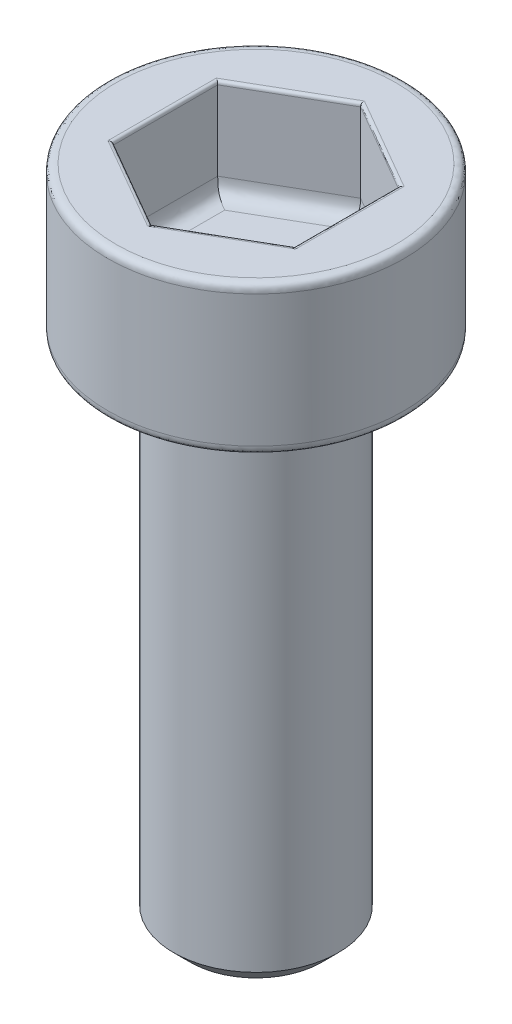
SolidWorks part; units mm, degrees
ref_plane "Front Plane" through (0, 0, 0) normal (0, 0, 1) x (1, 0, 0)
ref_plane "Top Plane" through (0, 0, 0) normal (0, 1, 0) x (1, 0, 0)
ref_plane "Right Plane" through (0, 0, 0) normal (1, 0, 0) x (0, 0, -1)
sketch "Sketch2" plane through (0, 0, 0) normal (1, 0, 0) x (0, 0, -1)
  line L0 (0, 0) -> (0, 40)
  line L1 (0, 40) -> (9, 40)
  line L2 (9, 40) -> (9, 31)
  line L3 (9, 31) -> (5, 31)
  line L4 (5, 31) -> (5, 0)
  line L5 (5, 0) -> (0, 0)
  dimension "D1" = 5
  dimension "D2" = 9
  dimension "D3" = 9
  dimension "D4" = 40
revolve "Revolve1" add sketch "Sketch2" angle 360 about L0
chamfer "Chamfer1" distance 1 angle 45 1 edges at (0, 0, -5)
sketch "Sketch3" plane through (0, 40, 0) normal (0, 1, 0) x (1, 0, 0)
  line L1 (0, 6.3509) -> (-5.5, 3.1754)
  line L2 (-5.5, 3.1754) -> (-5.5, -3.1754)
  line L3 (-5.5, -3.1754) -> (0, -6.3509)
  line L4 (0, -6.3509) -> (5.5, -3.1754)
  line L5 (5.5, -3.1754) -> (5.5, 3.1754)
  line L6 (5.5, 3.1754) -> (0, 6.3509)
  circle A0 centre (0, 0) radius 5.5 construction
  dimension "D1" = 11
extrude "Cut-Extrude1" cut sketch "Sketch3" against normal blind 6
fillet "Fillet1" radius 1 6 edges at (5.5, 34, 0) (2.75, 34, 4.7631) (-2.75, 34, 4.7631) (-5.5, 34, 0) (-2.75, 34, -4.7631) (2.75, 34, -4.7631) curvature continuous yes
fillet "Fillet2" radius 0.5 2 edges at (0, 31, -9) (0, 40, -9) curvature continuous yes
ref_axis "Axis1" through (0, 36, 0) along (0, -1, 0)
fillet "Fillet3" radius 0.2 6 edges at (-5.5, 40, 0) (-2.75, 40, 4.7631) (2.75, 40, 4.7631) (5.5, 40, 0) (2.75, 40, -4.7631) (-2.75, 40, -4.7631) curvature continuous yes
